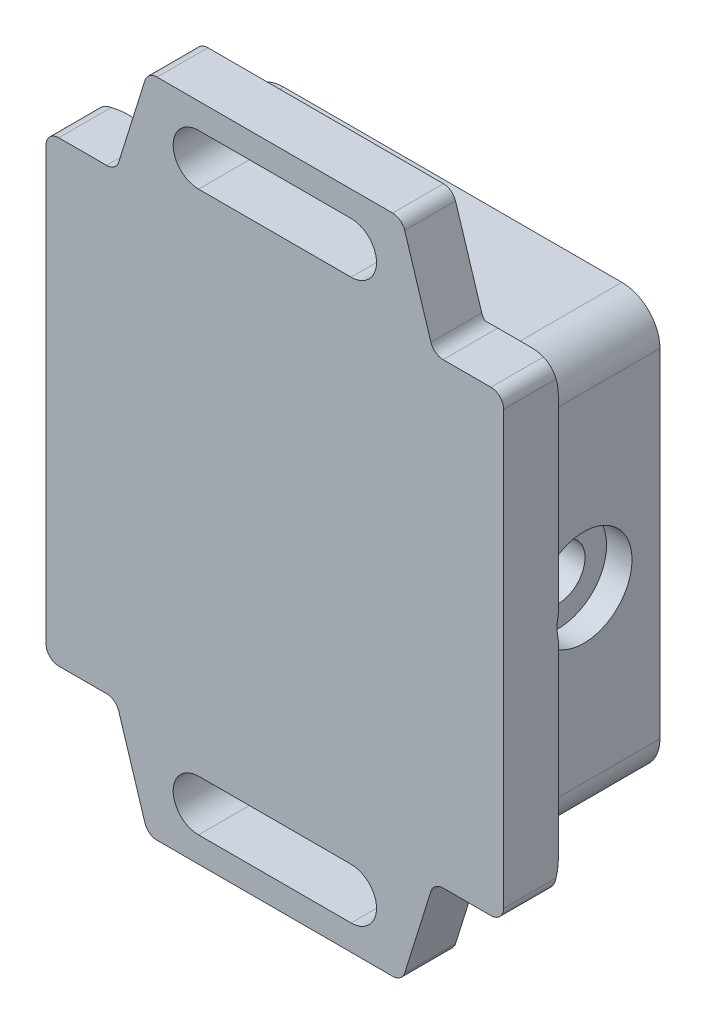
SolidWorks part; units mm, degrees
ref_plane "Plan de face" through (0, 0, 0) normal (0, 0, 1) x (1, 0, 0)
ref_plane "Plan de dessus" through (0, 0, 0) normal (0, 1, 0) x (1, 0, 0)
ref_plane "Plan de droite" through (0, 0, 0) normal (1, 0, 0) x (0, 0, -1)
sketch "Esquisse1" plane through (0, 0, 0) normal (0, 0, 1) x (1, 0, 0)
  line L1 (10.3, 10.3) -> (-10.3, 10.3)
  line L2 (10.3, 10.3) -> (10.3, -10.3)
  line L3 (10.3, -10.3) -> (-10.3, -10.3)
  line L4 (-10.3, 10.3) -> (-10.3, -10.3)
  line L5 (10.3, 10.3) -> (-10.3, -10.3) construction
  line L6 (10.3, -10.3) -> (-10.3, 10.3) construction
  line L7 (16.3, 16.3) -> (-16.3, 16.3)
  line L8 (16.3, 16.3) -> (16.3, -16.3)
  line L9 (16.3, -16.3) -> (-16.3, -16.3)
  line L10 (-16.3, 16.3) -> (-16.3, -16.3)
  line L11 (16.3, 16.3) -> (-16.3, -16.3) construction
  line L12 (16.3, -16.3) -> (-16.3, 16.3) construction
  point P0 (0, 0)
  point P6 (0, 0)
  dimension "D1" = 20.6
  dimension "D2" = 6
  dimension "D3" = 6
extrude "Boss.-Extru.1" add sketch "Esquisse1" along normal blind 10
sketch "Esquisse2" plane through (0, 0, 10) normal (0, 0, 1) x (1, 0, 0)
  line L2 (18, 18) -> (-18, 18)
  line L3 (18, 18) -> (18, -18)
  line L4 (18, -18) -> (-18, -18)
  line L5 (-10.3, 10.3) -> (-10.3, -10.3)
  line L6 (10.3, 10.3) -> (-10.3, 10.3)
  line L7 (10.3, -10.3) -> (10.3, 10.3)
  line L8 (-10.3, -10.3) -> (10.3, -10.3)
  line L9 (-10.3, 10.3) -> (-10.3, -10.3)
  line L10 (10.3, 10.3) -> (-10.3, 10.3)
  line L11 (10.3, -10.3) -> (10.3, 10.3)
  line L12 (-10.3, -10.3) -> (10.3, -10.3)
  line L13 (-18, 18) -> (-18, -18)
  line L14 (18, 18) -> (-18, -18) construction
  line L15 (18, -18) -> (-18, 18) construction
  point P0 (0, 0)
  dimension "D2" = 36
  dimension "D3" = 36
  dimension "D1" = 0
extrude "Boss.-Extru.2" add sketch "Esquisse2" along normal blind 4
sketch "Esquisse3" plane through (0, 0, 14) normal (0, 0, 1) x (1, 0, 0)
  line L0 (0, 0) -> (18, 0) construction
  line L1 (18, -18) -> (18, 18) construction
  line L2 (0, 18) -> (0, 0) construction
  line L3 (18, 18) -> (-18, 18) construction
  line L4 (12.5, 18) -> (-12.5, 18)
  line L5 (-12.5, 18) -> (-10, 26)
  line L6 (-10, 26) -> (10, 26)
  line L7 (0, 18) -> (0, 26) construction
  line L8 (12.5, 18) -> (10, 26)
  line L9 (0, -18) -> (0, -26) construction
  line L10 (12.5, -18) -> (10, -26)
  line L11 (-10, -26) -> (10, -26)
  line L12 (-12.5, -18) -> (-10, -26)
  line L13 (12.5, -18) -> (-12.5, -18)
  line L14 (-6, 22) -> (6, 22) construction
  line L15 (-6, 24) -> (6, 24)
  line L16 (-6, 20) -> (6, 20)
  line L17 (-6, -22) -> (6, -22) construction
  line L18 (-6, -24) -> (6, -24)
  line L19 (-6, -20) -> (6, -20)
  arc A0 (-6, 24) -> (-6, 20) centre (-6, 22) ccw
  arc A1 (6, 20) -> (6, 24) centre (6, 22) ccw
  arc A2 (-6, -24) -> (-6, -20) centre (-6, -22) cw
  arc A3 (6, -20) -> (6, -24) centre (6, -22) cw
  point P21 (0, 22)
  point P28 (0, -22)
  dimension "D1" = 8
  dimension "D2" = 25
  dimension "D3" = 20
  dimension "D4" = 4
  dimension "D5" = 12
extrude "Boss.-Extru.3" add sketch "Esquisse3" against normal blind 4
chamfer "Chanfrein1" distance 2 angle 45 4 edges at (0, -16.3, 10) (16.3, 0, 10) (0, 16.3, 10) (-16.3, 0, 10)
fillet "Congé1" radius 1 16 edges at (18, -18, 11.85) (12.5, -18, 11.85) (10, -26, 12) (-10, -26, 12) (-12.5, -18, 11.85) (-18, -18, 11.85) (-12.5, 18, 11.85) (-18, 18, 11.85) (18, 18, 11.85) (12.5, 18, 11.85) (-10, 26, 12) (10, 26, 12) (10.3, -10.3, 7) (10.3, 10.3, 7) (-10.3, 10.3, 7) (-10.3, -10.3, 7)
fillet "Congé2" radius 3 8 edges at (17.0036, -17.0036, 8.7036) (-17.0036, -17.0036, 8.7036) (-17.0036, 17.0036, 8.7036) (17.0036, 17.0036, 8.7036) (16.3, 16.3, 4) (16.3, -16.3, 4) (-16.3, 16.3, 4) (-16.3, -16.3, 4)
sketch "Esquisse4" plane through (0, 0, 14) normal (0, 0, 1) x (1, 0, 0)
  line L5 (-9.3, -10.3) -> (9.3, -10.3)
  line L6 (-10.3, 9.3) -> (-10.3, -9.3)
  line L7 (9.3, 10.3) -> (-9.3, 10.3)
  line L8 (10.3, -9.3) -> (10.3, 9.3)
  line L9 (-9.3, -10.3) -> (9.3, -10.3)
  line L10 (-10.3, 9.3) -> (-10.3, -9.3)
  line L11 (9.3, 10.3) -> (-9.3, 10.3)
  line L12 (10.3, -9.3) -> (10.3, 9.3)
  arc A4 (-10.3, -9.3) -> (-9.3, -10.3) centre (-9.3, -9.3) ccw
  arc A5 (-9.3, 10.3) -> (-10.3, 9.3) centre (-9.3, 9.3) ccw
  arc A6 (10.3, 9.3) -> (9.3, 10.3) centre (9.3, 9.3) ccw
  arc A7 (9.3, -10.3) -> (10.3, -9.3) centre (9.3, -9.3) ccw
  arc A8 (-10.3, -9.3) -> (-9.3, -10.3) centre (-9.3, -9.3) ccw
  arc A9 (-9.3, 10.3) -> (-10.3, 9.3) centre (-9.3, 9.3) ccw
  arc A10 (10.3, 9.3) -> (9.3, 10.3) centre (9.3, 9.3) ccw
  arc A11 (9.3, -10.3) -> (10.3, -9.3) centre (9.3, -9.3) ccw
  dimension "D1" = 0
extrude "Boss.-Extru.4" add sketch "Esquisse4" against normal blind 1
chamfer "Chanfrein2" distance 1 angle 45 8 edges at (0, -10.3, 0) (10.0071, -10.0071, 0) (-10.0071, -10.0071, 0) (10.3, 0, 0) (-10.3, 0, 0) (10.0071, 10.0071, 0) (-10.0071, 10.0071, 0) (0, 10.3, 0)
sketch "Esquisse5" plane through (16.3, 0, 0) normal (1, 0, 0) x (0, 0, -1)
  line L0 (0, -13.3) -> (0, 13.3) construction
  circle A0 centre (-6, 0) radius 2.1
  point P4 (0, 0)
  dimension "D1" = 4.2
  dimension "D2" = 6
extrude "Enlèv. mat.-Extru.1" cut sketch "Esquisse5" against normal blind 10
sketch "Esquisse6" plane through (16.3, 0, 0) normal (1, 0, 0) x (0, 0, -1)
  circle A0 centre (-6, 0) radius 3.8
  dimension "D1" = 7.6
extrude "Enlèv. mat.-Extru.2" cut sketch "Esquisse6" along normal blind 10 and the other way blind 2
